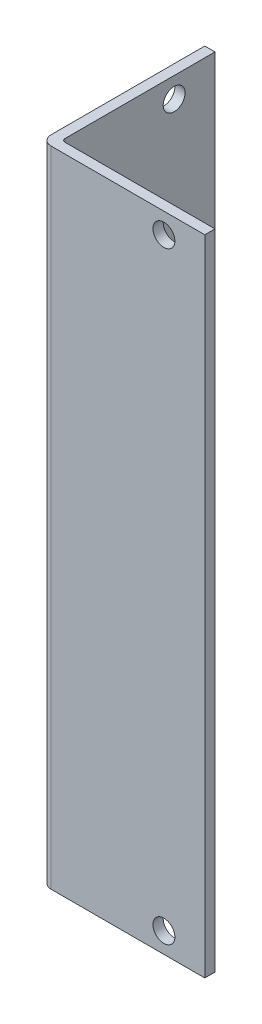
SolidWorks part; units mm, degrees
material "6061-T6 (SS)"
ref_plane "Front Plane" through (0, 0, 0) normal (0, 0, 1) x (1, 0, 0)
ref_plane "Top Plane" through (0, 0, 0) normal (0, 1, 0) x (1, 0, 0)
ref_plane "Right Plane" through (0, 0, 0) normal (1, 0, 0) x (0, 0, -1)
sketch "Sketch1" plane through (0, 0, 0) normal (0, 1, 0) x (1, 0, 0)
  line L1 (-12.7, -12.7) -> (12.7, -12.7)
  line L2 (-12.7, -12.7) -> (-12.7, 12.7)
  line L3 (-12.7, 12.7) -> (12.7, 12.7)
  line L4 (12.7, -12.7) -> (12.7, 12.7)
  line L5 (-12.7, -12.7) -> (12.7, 12.7) construction
  line L6 (-12.7, 12.7) -> (12.7, -12.7) construction
  point P0 (0, 0)
  dimension "D1" = 25.4
  dimension "D2" = 25.4
extrude "Boss-Extrude1" add sketch "Sketch1" along normal mid plane 113.5
sketch "Sketch2" plane through (0, 56.75, 0) normal (0, 1, 0) x (1, 0, 0)
  line L0 (-12.7, 12.7) -> (-12.7, -12.7) construction
  line L1 (12.7, 12.7) -> (-11.1125, 12.7)
  line L2 (12.7, 12.7) -> (12.7, -11.1125)
  line L3 (12.7, -11.1125) -> (-11.1125, -11.1125)
  line L4 (-11.1125, 12.7) -> (-11.1125, -11.1125)
  line L5 (-12.7, -12.7) -> (12.7, -12.7) construction
  dimension "D1" = 1.5875
  dimension "D2" = 1.5875
extrude "Cut-Extrude1" cut sketch "Sketch2" against normal through all
fillet "Fillet1" radius 0.508 1 edges at (-11.1125, 0, 11.1125)
hole_wizard "M3 Clearance Hole1" positions "Sketch3" profile "Sketch4" hole size "M3" standard "ANSI Metric" end condition through all
sketch "Sketch3" plane through (0, 0, 12.7) normal (0, 0, 1) x (1, 0, 0)
  line L1 (-12.7, 56.75) -> (12.7, 56.75) construction
  line L2 (12.7, 56.75) -> (12.7, -56.75) construction
  point P0 (6.35, 47.075)
  dimension "D1" = 6.35
  dimension "D2" = 9.675
sketch "Sketch4" plane through (6.35, 47.075, 12.7) normal (1, 0, 0) x (0, -1, 0)
  line L0 (0, 0) -> (0, 25.4)
  line L1 (0, 25.4) -> (1.7, 25.4)
  line L2 (1.7, 25.4) -> (1.7, 0)
  line L5 (1.7, 0) -> (0, 0)
  line L11 (0, -6.35) -> (0, 107.95) construction
  dimension "Thru Hole Dia." = 3.4
  dimension "Thru Hole Depth" = 25.4
hole_wizard "M3 Clearance Hole2" positions "Sketch5" profile "Sketch6" hole size "M3" standard "ANSI Metric" end condition through all
sketch "Sketch5" plane through (-12.7, 0, 0) normal (-1, 0, 0) x (0, 0, 1)
  line L1 (-12.7, 56.75) -> (12.7, 56.75) construction
  line L2 (-12.7, 56.75) -> (-12.7, -56.75) construction
  point P0 (-6.35, 47.075)
  dimension "D1" = 6.35
  dimension "D2" = 9.675
sketch "Sketch6" plane through (-12.7, 47.075, -6.35) normal (0, 1, 0) x (0, 0, 1)
  line L0 (0, 0) -> (0, 25.4)
  line L1 (0, 25.4) -> (1.7, 25.4)
  line L2 (1.7, 25.4) -> (1.7, 0)
  line L5 (1.7, 0) -> (0, 0)
  line L11 (0, -6.35) -> (0, 107.95) construction
  dimension "Thru Hole Dia." = 3.4
  dimension "Thru Hole Depth" = 25.4
hole_wizard "M3 Clearance Hole3" positions "Sketch7" profile "Sketch8" hole size "M3" standard "ANSI Metric" end condition through all
sketch "Sketch7" plane through (0, 0, 12.7) normal (0, 0, 1) x (1, 0, 0)
  line L2 (-12.7, -56.75) -> (12.7, -56.75) construction
  line L3 (12.7, 56.75) -> (12.7, -56.75) construction
  point P0 (6.35, -46.575)
  dimension "D1" = 6.35
  dimension "D2" = 10.175
sketch "Sketch8" plane through (6.35, -46.575, 12.7) normal (1, 0, 0) x (0, -1, 0)
  line L0 (0, 0) -> (0, 25.4)
  line L1 (0, 25.4) -> (1.7, 25.4)
  line L2 (1.7, 25.4) -> (1.7, 0)
  line L5 (1.7, 0) -> (0, 0)
  line L11 (0, -6.35) -> (0, 107.95) construction
  dimension "Thru Hole Dia." = 3.4
  dimension "Thru Hole Depth" = 25.4
hole_wizard "M3 Clearance Hole4" positions "Sketch9" profile "Sketch10" hole size "M3" standard "ANSI Metric" end condition through all
sketch "Sketch9" plane through (-12.7, 0, 0) normal (-1, 0, 0) x (0, 0, 1)
  line L1 (-12.7, -56.75) -> (12.7, -56.75) construction
  line L2 (-12.7, 56.75) -> (-12.7, -56.75) construction
  point P0 (-6.35, -46.575)
  dimension "D1" = 6.35
  dimension "D2" = 10.175
sketch "Sketch10" plane through (-12.7, -46.575, -6.35) normal (0, 1, 0) x (0, 0, 1)
  line L0 (0, 0) -> (0, 25.4)
  line L1 (0, 25.4) -> (1.7, 25.4)
  line L2 (1.7, 25.4) -> (1.7, 0)
  line L5 (1.7, 0) -> (0, 0)
  line L11 (0, -6.35) -> (0, 107.95) construction
  dimension "Thru Hole Dia." = 3.4
  dimension "Thru Hole Depth" = 25.4
fillet "Fillet2" radius 1.5 1 edges at (-12.7, 0, 12.7)
sketch "Sketch11" plane through (-12.7, 0, 0) normal (-1, 0, 0) x (0, 0, 1)
  line L0 (12.7, 56.75) -> (12.7, -56.75) construction
  line L1 (-12.7, 56.75) -> (4.2, 56.75)
  line L2 (-12.7, 56.75) -> (-12.7, 50.25)
  line L3 (-12.7, 50.25) -> (4.2, 50.25)
  line L4 (4.2, 56.75) -> (4.2, 50.25)
  line L6 (-12.7, -56.75) -> (4.2, -56.75)
  line L7 (-12.7, -56.75) -> (-12.7, -49.75)
  line L8 (-12.7, -49.75) -> (4.2, -49.75)
  line L9 (4.2, -56.75) -> (4.2, -49.75)
  dimension "D1" = 8.5
  dimension "D2" = 6.5
  dimension "D3" = 7
extrude "Cut-Extrude2" cut sketch "Sketch11" against normal up to next
sketch "Sketch12" plane through (0, 0, 12.7) normal (0, 0, 1) x (1, 0, 0)
  line L0 (-12.7, -56.75) -> (-12.7, 56.75) construction
  line L1 (12.7, 56.75) -> (-4.2, 56.75)
  line L2 (12.7, 56.75) -> (12.7, 50.25)
  line L3 (12.7, 50.25) -> (-4.2, 50.25)
  line L4 (-4.2, 56.75) -> (-4.2, 50.25)
  line L5 (12.7, -56.75) -> (-4.2, -56.75)
  line L6 (12.7, -56.75) -> (12.7, -49.75)
  line L7 (12.7, -49.75) -> (-4.2, -49.75)
  line L8 (-4.2, -56.75) -> (-4.2, -49.75)
  dimension "D1" = 8.5
  dimension "D2" = 7
  dimension "D3" = 8.5
  dimension "D4" = 6.5
extrude "Cut-Extrude3" cut sketch "Sketch12" against normal up to next
fillet "Fillet3" radius 3.81 4 edges at (-4.2, -49.75, 11.9062) (-11.9063, -49.75, 4.2) (-11.9063, 50.25, 4.2) (-4.2, 50.25, 11.9062)
sketch "Sketch13" plane through (-12.7, 0, 0) normal (-1, 0, 0) x (0, 0, 1)
  line L0 (4.2, -56.75) -> (4.2, 56.75) construction
  line L9 (2.7, -56.75) -> (2.7, 56.75) construction
  line L10 (-12.7, 50.25) -> (-12.7, -49.75) construction
  line L11 (2.7, -43.4) -> (-12.7, -43.4)
  line L12 (2.7, -43.4) -> (2.7, 43.9)
  line L13 (2.7, 43.9) -> (-12.7, 43.9)
  line L14 (-12.7, -43.4) -> (-12.7, 43.9)
  circle A2 centre (-6.35, 47.075) radius 1.7 construction
  circle A3 centre (-6.35, -46.575) radius 1.7 construction
  dimension "D2" = 3.175
  dimension "D3" = 3.175
  dimension "D1" = 1.5
extrude "Cut-Extrude4" cut sketch "Sketch13" against normal up to next
sketch "Sketch14" plane through (0, 0, 12.7) normal (0, 0, 1) x (1, 0, 0)
  line L0 (-4.2, 56.75) -> (-4.2, -56.75) construction
  line L1 (-2.7, 56.75) -> (-2.7, -56.75) construction
  line L2 (12.7, 50.25) -> (12.7, -49.75) construction
  line L3 (-2.7, -43.4) -> (12.7, -43.4)
  line L4 (-2.7, -43.4) -> (-2.7, 43.9)
  line L5 (-2.7, 43.9) -> (12.7, 43.9)
  line L6 (12.7, -43.4) -> (12.7, 43.9)
  circle A0 centre (6.35, 47.075) radius 1.7 construction
  circle A1 centre (6.35, -46.575) radius 1.7 construction
  dimension "D2" = 3.175
  dimension "D3" = 3.175
  dimension "D1" = 1.5
extrude "Cut-Extrude5" cut sketch "Sketch14" against normal up to next
chamfer "Chamfer2" distance 6.35 angle 45 4 edges at (-11.9063, 43.9, 2.7) (-2.7, 43.9, 11.9062) (-2.7, -43.4, 11.9062) (-11.9062, -43.4, 2.7)
fillet "Fillet5" radius 3.81 8 edges at (3.65, -43.4, 11.9062) (-2.7, -37.05, 11.9062) (-11.9063, -43.4, -3.65) (-11.9063, -37.05, 2.7) (-11.9063, 43.9, -3.65) (-11.9063, 37.55, 2.7) (-2.7, 37.55, 11.9062) (3.65, 43.9, 11.9062)
sketch "Sketch15" plane through (0, 56.75, 0) normal (0, 1, 0) x (1, 0, 0)
  line L0 (-11.2, -12.7) -> (-4.2, -12.7) construction
  line L1 (-12.7, -12.7) -> (-0.39, -12.7)
  line L2 (-12.7, -12.7) -> (-12.7, -0.39)
  line L3 (-12.7, -0.39) -> (-0.39, -0.39)
  line L4 (-0.39, -12.7) -> (-0.39, -0.39)
  line L5 (-12.7, -4.2) -> (-12.7, -11.2) construction
  line L6 (-0.39, -11.1125) -> (-0.39, -12.7) construction
extrude "Cut-Extrude6" cut sketch "Sketch15" against normal up to surface (6.5 mm away) up to face at (6.155, 50.25, 11.9062)
sketch "Sketch16" plane through (0, 50.25, 0) normal (0, 1, 0) x (1, 0, 0)
  line L0 (-11.2, -12.7) -> (12.7, -12.7) construction
  line L1 (-12.7, -12.7) -> (-5.7, -12.7)
  line L2 (-12.7, -12.7) -> (-12.7, -5.7)
  line L3 (-12.7, -5.7) -> (-5.7, -5.7)
  line L4 (-5.7, -12.7) -> (-5.7, -5.7)
  line L5 (-12.7, 12.7) -> (-12.7, -11.2) construction
  dimension "D1" = 7
  dimension "D2" = 7
sketch "Sketch17" plane through (0, -56.75, 0) normal (0, -1, 0) x (1, 0, 0)
  line L0 (-11.2, 12.7) -> (-4.2, 12.7) construction
  line L1 (-12.7, 12.7) -> (-0.39, 12.7)
  line L2 (-12.7, 12.7) -> (-12.7, 0.39)
  line L3 (-12.7, 0.39) -> (-0.39, 0.39)
  line L4 (-0.39, 12.7) -> (-0.39, 0.39)
  line L5 (-12.7, 4.2) -> (-12.7, 11.2) construction
  line L6 (-11.1125, 0.39) -> (-12.7, 0.39) construction
  line L7 (-0.39, 12.7) -> (-0.39, 11.1125) construction
extrude "Cut-Extrude8" cut sketch "Sketch17" against normal up to surface (7 mm away) up to face at (6.155, -49.75, 11.9062)
sketch "Sketch18" plane through (-12.7, 0, 0) normal (-1, 0, 0) x (0, 0, 1)
  line L0 (-12.7, -43.4) -> (-5.2282, -43.4) construction
  line L1 (5.7, -43.4) -> (11.2, -43.4)
  line L2 (5.7, -43.4) -> (5.7, -40.4)
  line L3 (5.7, -40.4) -> (11.2, -40.4)
  line L4 (11.2, -43.4) -> (11.2, -40.4)
  line L5 (12.7, 50.25) -> (12.7, -49.75) construction
  point P8 (8.45, -40.4)
  dimension "D1" = 5.5
  dimension "D2" = 3
  dimension "D3" = 4.25
sketch "Sketch19" plane through (0, -49.75, 0) normal (0, -1, 0) x (1, 0, 0)
  line L0 (12.7, 12.7) -> (-11.2, 12.7) construction
  line L1 (-12.7, 5.7) -> (-5.7, 5.7)
  line L2 (-12.7, 5.7) -> (-12.7, 12.7)
  line L3 (-12.7, 12.7) -> (-5.7, 12.7)
  line L4 (-5.7, 5.7) -> (-5.7, 12.7)
  line L5 (-12.7, 11.2) -> (-12.7, -12.7) construction
sketch "Sketch20" plane through (-12.7, 0, 0) normal (-1, 0, 0) x (0, 0, 1)
  line L0 (-12.7, 43.9) -> (-12.7, -43.4)
  line L13 (7.2, -40.4) -> (11.2, -40.4)
  line L14 (11.2, -40.4) -> (11.2, 50.25)
  line L15 (11.2, 50.25) -> (-12.7, 50.25)
  line L16 (-12.7, 50.25) -> (-12.7, 43.9)
  line L17 (-12.7, 43.9) -> (-5.2282, 43.9)
  line L18 (-2.5341, 42.7841) -> (1.5841, 38.6659)
  line L19 (2.7, 35.9718) -> (2.7, -35.4718)
  line L20 (1.5841, -38.1659) -> (-2.5341, -42.2841)
  line L21 (-5.2282, -43.4) -> (-12.7, -43.4)
  line L22 (-12.7, -43.4) -> (-12.7, -49.75)
  line L23 (-12.7, -49.75) -> (11.2, -49.75)
  line L24 (11.2, -49.75) -> (11.2, -43.4)
  line L25 (11.2, -43.4) -> (7.2, -43.4)
  line L26 (7.2, -40.4) -> (11.2, -40.4)
  line L27 (11.2, -40.4) -> (11.2, 50.25)
  line L28 (11.2, 50.25) -> (-12.7, 50.25)
  line L29 (-12.7, 50.25) -> (-12.7, 43.9)
  line L30 (-12.7, 43.9) -> (-5.2282, 43.9)
  line L31 (-2.5341, 42.7841) -> (1.5841, 38.6659)
  line L32 (2.7, 35.9718) -> (2.7, -35.4718)
  line L33 (1.5841, -38.1659) -> (-2.5341, -42.2841)
  line L34 (-5.2282, -43.4) -> (-12.7, -43.4)
  line L35 (-12.7, -43.4) -> (-12.7, -49.75)
  line L36 (-12.7, -49.75) -> (11.2, -49.75)
  line L37 (11.2, -49.75) -> (11.2, -43.4)
  line L38 (11.2, -43.4) -> (7.2, -43.4)
  arc A5 (7.2, -40.4) -> (7.2, -43.4) centre (7.2, -41.9) ccw
  arc A6 (-2.5341, 42.7841) -> (-5.2282, 43.9) centre (-5.2282, 40.09) ccw
  arc A7 (2.7, 35.9718) -> (1.5841, 38.6659) centre (-1.11, 35.9718) ccw
  arc A8 (1.5841, -38.1659) -> (2.7, -35.4718) centre (-1.11, -35.4718) ccw
  arc A9 (-5.2282, -43.4) -> (-2.5341, -42.2841) centre (-5.2282, -39.59) ccw
  arc A10 (7.2, -40.4) -> (7.2, -43.4) centre (7.2, -41.9) ccw
  arc A11 (-2.5341, 42.7841) -> (-5.2282, 43.9) centre (-5.2282, 40.09) ccw
  arc A12 (2.7, 35.9718) -> (1.5841, 38.6659) centre (-1.11, 35.9718) ccw
  arc A13 (1.5841, -38.1659) -> (2.7, -35.4718) centre (-1.11, -35.4718) ccw
  arc A14 (-5.2282, -43.4) -> (-2.5341, -42.2841) centre (-5.2282, -39.59) ccw
  line M26 (-12.7, 43.9) -> (-5.2282, 43.9)
  arc M27 (-5.2282, 43.9) -> (-2.5341, 42.7841) centre (-5.2282, 40.09) cw
  line M28 (-2.5341, 42.7841) -> (1.5841, 38.6659)
  arc M29 (1.5841, 38.6659) -> (2.7, 35.9718) centre (-1.11, 35.9718) cw
  line M30 (2.7, 35.9718) -> (2.7, -35.4718)
  arc M31 (2.7, -35.4718) -> (1.5841, -38.1659) centre (-1.11, -35.4718) cw
  line M32 (1.5841, -38.1659) -> (-2.5341, -42.2841)
  arc M33 (-2.5341, -42.2841) -> (-5.2282, -43.4) centre (-5.2282, -39.59) cw
  line M34 (-5.2282, -43.4) -> (-12.7, -43.4)
  dimension "D1" = 0
extrude "Boss-Extrude2" add sketch "Sketch20" against normal up to surface (1.5875 mm away) contours L0 M26 M34 M33 M32 M31 M30 M29 M28 M27 region at (-12.7, 0.25, -5.177) up to face at (-11.1125, -46.575, -4.65)
sketch "Sketch21" plane through (0, 0, 12.7) normal (0, 0, 1) x (1, 0, 0)
  line L0 (12.7, 43.9) -> (12.7, -43.4)
  line L14 (-11.2, 50.25) -> (-11.2, -49.75)
  line L15 (-11.2, -49.75) -> (12.7, -49.75)
  line L16 (12.7, -49.75) -> (12.7, -43.4)
  line L17 (12.7, -43.4) -> (5.2282, -43.4)
  line L18 (2.5341, -42.2841) -> (-1.5841, -38.1659)
  line L19 (-2.7, -35.4718) -> (-2.7, 35.9718)
  line L20 (-1.5841, 38.6659) -> (2.5341, 42.7841)
  line L21 (5.2282, 43.9) -> (12.7, 43.9)
  line L22 (12.7, 43.9) -> (12.7, 50.25)
  line L23 (12.7, 50.25) -> (-11.2, 50.25)
  line L27 (-11.2, 50.25) -> (-11.2, -49.75)
  line L28 (-11.2, -49.75) -> (12.7, -49.75)
  line L29 (12.7, -49.75) -> (12.7, -43.4)
  line L30 (12.7, -43.4) -> (5.2282, -43.4)
  line L31 (2.5341, -42.2841) -> (-1.5841, -38.1659)
  line L32 (-2.7, -35.4718) -> (-2.7, 35.9718)
  line L33 (-1.5841, 38.6659) -> (2.5341, 42.7841)
  line L34 (5.2282, 43.9) -> (12.7, 43.9)
  line L35 (12.7, 43.9) -> (12.7, 50.25)
  line L36 (12.7, 50.25) -> (-11.2, 50.25)
  arc A6 (2.5341, -42.2841) -> (5.2282, -43.4) centre (5.2282, -39.59) ccw
  arc A7 (-2.7, -35.4718) -> (-1.5841, -38.1659) centre (1.11, -35.4718) ccw
  arc A8 (-1.5841, 38.6659) -> (-2.7, 35.9718) centre (1.11, 35.9718) ccw
  arc A9 (5.2282, 43.9) -> (2.5341, 42.7841) centre (5.2282, 40.09) ccw
  arc A11 (2.5341, -42.2841) -> (5.2282, -43.4) centre (5.2282, -39.59) ccw
  arc A12 (-2.7, -35.4718) -> (-1.5841, -38.1659) centre (1.11, -35.4718) ccw
  arc A13 (-1.5841, 38.6659) -> (-2.7, 35.9718) centre (1.11, 35.9718) ccw
  arc A14 (5.2282, 43.9) -> (2.5341, 42.7841) centre (5.2282, 40.09) ccw
  line M24 (12.7, -43.4) -> (5.2282, -43.4)
  arc M25 (5.2282, -43.4) -> (2.5341, -42.2841) centre (5.2282, -39.59) cw
  line M26 (2.5341, -42.2841) -> (-1.5841, -38.1659)
  arc M27 (-1.5841, -38.1659) -> (-2.7, -35.4718) centre (1.11, -35.4718) cw
  line M28 (-2.7, -35.4718) -> (-2.7, 35.9718)
  arc M29 (-2.7, 35.9718) -> (-1.5841, 38.6659) centre (1.11, 35.9718) cw
  line M30 (-1.5841, 38.6659) -> (2.5341, 42.7841)
  arc M31 (2.5341, 42.7841) -> (5.2282, 43.9) centre (5.2282, 40.09) cw
  line M32 (5.2282, 43.9) -> (12.7, 43.9)
  dimension "D1" = 0
sketch "Sketch22" plane through (0, 50.25, 0) normal (0, 1, 0) x (1, 0, 0)
  line L0 (-12.7, 12.7) -> (-12.7, -11.2) construction
  line L1 (-12.7, -12.7) -> (-4.1125, -12.7)
  line L2 (-12.7, -12.7) -> (-12.7, -4.1125)
  line L3 (-12.7, -4.1125) -> (-4.1125, -4.1125)
  line L4 (-4.1125, -12.7) -> (-4.1125, -4.1125)
  line L5 (12.7, -12.7) -> (-11.2, -12.7) construction
  line L6 (12.7, -11.1125) -> (-10.6045, -11.1125) construction
  dimension "D1" = 7
extrude "Boss-Extrude3" add sketch "Sketch21" against normal up to surface (1.5875 mm away) contours L0 M32 M31 M30 M29 M28 M27 M26 M25 M24 region at (5.177, 0.25, 12.7) up to face at (8.05, -46.575, 11.1125)
